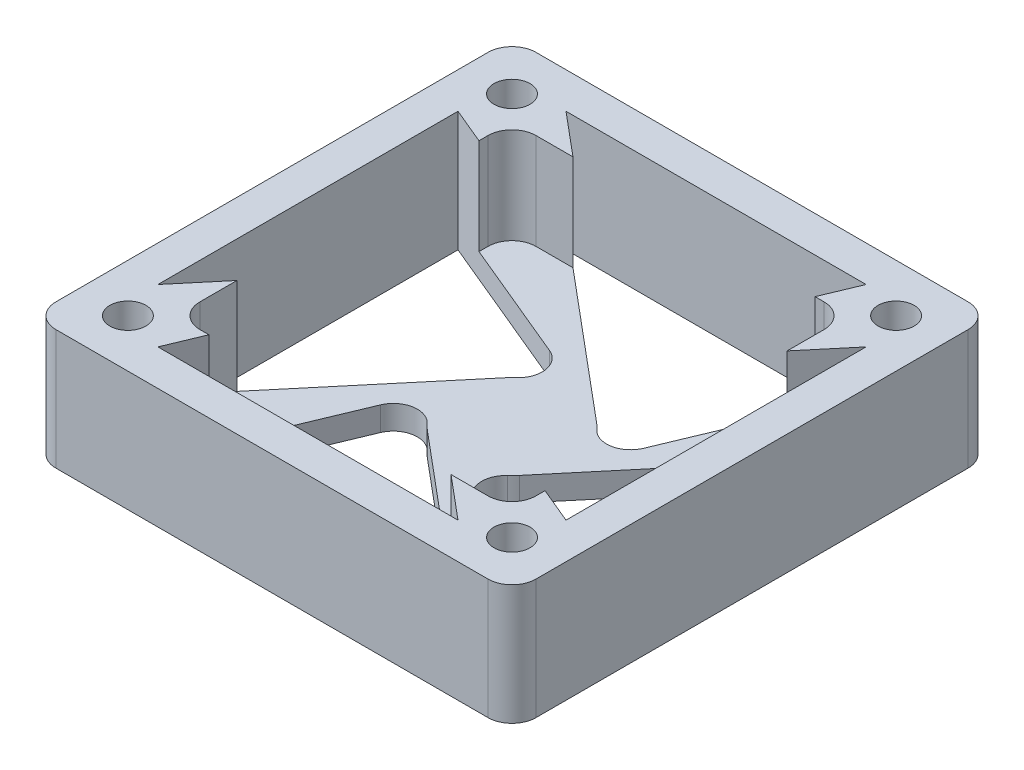
SolidWorks part; units mm, degrees
ref_plane "前视基准面" through (0, 0, 0) normal (0, 0, 1) x (1, 0, 0)
ref_plane "上视基准面" through (0, 0, 0) normal (0, 1, 0) x (1, 0, 0)
ref_plane "右视基准面" through (0, 0, 0) normal (1, 0, 0) x (0, 0, -1)
other "Configuration Table"
sketch "草图1" plane through (0, 0, 0) normal (0, 1, 0) x (1, 0, 0)
  line L1 (0, 0) -> (40, 0)
  line L2 (0, 0) -> (0, 40)
  line L3 (0, 40) -> (40, 40)
  line L4 (40, 0) -> (40, 40)
  dimension "D1" = 40
  dimension "D2" = 40
extrude "凸台-拉伸1" add sketch "草图1" along normal blind 10
fillet "圆角1" radius 2 4 edges at (0, 5, -40) (40, 5, -40) (40, 5, 0) (0, 5, 0)
sketch "草图2" plane through (0, 10, 0) normal (0, 1, 0) x (1, 0, 0)
  line L20 (6, 6) -> (34, 6)
  line L21 (34, 6) -> (34, 34)
  line L22 (34, 34) -> (6, 34)
  line L23 (6, 34) -> (6, 6)
  line L24 (6, 6) -> (34, 6)
  line L25 (34, 6) -> (34, 34)
  line L26 (34, 34) -> (6, 34)
  line L27 (6, 34) -> (6, 6)
  dimension "D1" = 6
extrude "切除-拉伸1" cut sketch "草图2" against normal blind 8
fillet "圆角2" radius 2 4 edges at (34, 6, -6) (6, 6, -6) (34, 6, -34) (6, 6, -34)
sketch "草图3" plane through (0, 10, 0) normal (0, 1, 0) x (1, 0, 0)
  line L0 (20, 40) -> (20, -2.4975) construction
  line L1 (38, 40) -> (2, 40) construction
  line L2 (0, 20) -> (44.4379, 20) construction
  line L3 (0, 38) -> (0, 2) construction
  circle A0 centre (4, 36) radius 1.5
  circle A1 centre (4, 4) radius 1.5
  circle A2 centre (36, 4) radius 1.5
  circle A3 centre (36, 36) radius 1.5
  dimension "D1" = 3
  dimension "D2" = 32
  dimension "D3" = 32
extrude "切除-拉伸2" cut sketch "草图3" against normal through all
sketch "草图4" plane through (0, 0, 0) normal (0, -1, 0) x (1, 0, 0)
  line L0 (20, 0) -> (20, -41.8307) construction
  line L1 (2, 0) -> (38, 0) construction
  line L2 (0, -20) -> (46.3164, -20) construction
  line L3 (0, -38) -> (0, -2) construction
  line L4 (16.1679, -23.2117) -> (3, -7.5)
  line L5 (3, -7.5) -> (3, -32.5)
  line L6 (21.9231, -24.6154) -> (3, -32.5)
  line L7 (15.3846, -21.9231) -> (7.5, -3)
  line L8 (32.5, -3) -> (7.5, -3)
  line L9 (16.7883, -16.1679) -> (32.5, -3)
  line L10 (18.0769, -15.3846) -> (37, -7.5)
  line L11 (37, -32.5) -> (37, -7.5)
  line L12 (23.8321, -16.7883) -> (37, -32.5)
  line L13 (24.6154, -18.0769) -> (32.5, -37)
  line L14 (7.5, -37) -> (32.5, -37)
  line L15 (23.2117, -23.8321) -> (7.5, -37)
  circle A0 centre (20, -20) radius 5
  circle A3 centre (20, -20) radius 2
  point P32 (20, -20)
  dimension "D1" = 10
  dimension "D2" = 3
  dimension "D3" = 25
  dimension "D4" = 4
extrude "切除-拉伸3" cut sketch "草图4" against normal through all contours A0 L4 L5 L6 | A0 L9 L8 L7 | A0 L12 L11 L10 | A0 L15 L14 L13 region at (8.3126, 0, -22.0499) region at (17.9501, 0, -8.3126) region at (22.0499, 0, -31.6874) region at (31.6874, 0, -17.9501)
fillet "圆角3" radius 2 4 edges at (15.3846, 1, -21.9231) (21.9231, 1, -24.6154) (24.6154, 1, -18.0769) (18.0769, 1, -15.3846)
